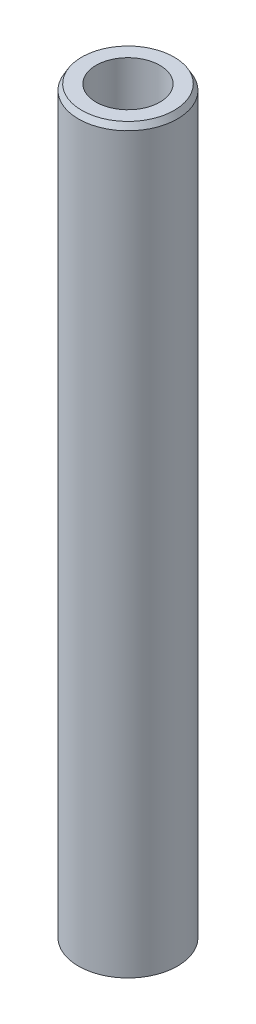
SolidWorks part; units mm, degrees
ref_plane "Front Plane" through (0, 0, 0) normal (0, 0, 1) x (1, 0, 0)
ref_plane "Top Plane" through (0, 0, 0) normal (0, 1, 0) x (1, 0, 0)
ref_plane "Right Plane" through (0, 0, 0) normal (1, 0, 0) x (0, 0, -1)
sketch "Sketch1" plane through (0, 0, 0) normal (0, 1, 0) x (1, 0, 0)
  circle A0 centre (0, 0) radius 40
  dimension "SHAFT_OD" = 80
extrude "Boss-Extrude1" add sketch "Sketch1" along normal blind 600
sketch "Sketch2" plane through (0, 0, 0) normal (0, 1, 0) x (1, 0, 0)
  circle A0 centre (0, 0) radius 25.7948
  dimension "BORE_D" = 51.5897
extrude "Cut-Extrude1" cut sketch "Sketch2" along normal through all
chamfer "Chamfer1" distance 4.6471 angle 30 2 edges at (0, 600, 40) (0, 0, 40) first distance on face at (0, 600, 40) first distance on face at (0, 0, 25.7948)
